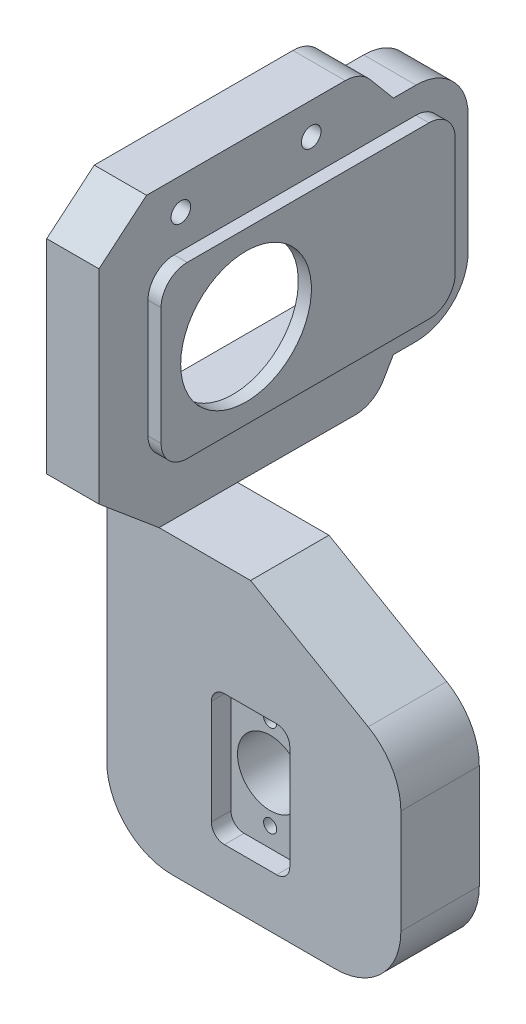
SolidWorks part; units mm, degrees
note: The reader was unsure of these and kept them because the rebuilt part matched: shared geometry of "Sketch1<3>", "Sketch1<4>", "Sketch3<4>", "Sketch3<6>", "Sketch3<7>".
other "Markup1"
sketch "Sketch8" plane through (0, 0, -51.7836) normal (-1, 0, 0) x (0, 0, 1)
material "ABS"
ref_plane "Front Plane" through (0, 0, 0) normal (0, 0, 1) x (1, 0, 0)
ref_plane "Top Plane" through (0, 0, 0) normal (0, 1, 0) x (1, 0, 0)
ref_plane "Right Plane" through (0, 0, 0) normal (1, 0, 0) x (0, 0, -1)
sketch "Sketch1" plane through (0, 0, 0) normal (0, 0, 1) x (1, 0, 0)
  line L0 (0, 45) -> (0, 10)
  line L1 (10, 0) -> (35, 0)
  line L2 (45, 10) -> (45, 25.9474)
  line L3 (40, 34.6077) -> (22, 45)
  line L4 (22, 45) -> (0, 45)
  line L6 (18, 8) -> (26, 8)
  line L7 (16, 10) -> (16, 26)
  line L8 (18, 28) -> (26, 28)
  line L9 (28, 10) -> (28, 26)
  line L10 (16, 8) -> (28, 28) construction
  line L11 (16, 28) -> (28, 8) construction
  circle A0 centre (22, 18) radius 5
  circle A1 centre (22, 11) radius 1
  circle A2 centre (22, 25) radius 1
  arc A3 (18, 8) -> (16, 10) centre (18, 10) cw
  arc A4 (26, 8) -> (28, 10) centre (26, 10) ccw
  arc A5 (26, 28) -> (28, 26) centre (26, 26) cw
  arc A6 (16, 26) -> (18, 28) centre (18, 26) cw
  arc A11 (45, 25.9474) -> (40, 34.6077) centre (35, 25.9474) ccw
  arc A12 (0, 10) -> (10, 0) centre (10, 10) ccw
  arc A13 (35, 0) -> (45, 10) centre (35, 10) ccw
  point P44 (0, 0)
  point P47 (45, 0)
  dimension "D5" = 10
  dimension "D7" = 2
  dimension "D4" = 2
  dimension "D16" = 10
  dimension "D1" = 45
  dimension "D2" = 45
  dimension "D3" = 120
  dimension "D6" = 7
  dimension "D8" = 7
  dimension "D9" = 27
  dimension "D10" = 22
  dimension "D11" = 20
  dimension "D12" = 11
  dimension "D13" = 6
  dimension "D14" = 10
extrude "Boss-Extrude1" add sketch "Sketch1" against normal blind 12 contours L4 L0 A12 L1 A13 L2 A11 L3
extrude "Cut-Extrude1" cut sketch "Sketch1<3>" against normal blind 3 contours A2 | A6 L7 A3 L6 A4 L9 A5 L8 A2 A1 | A1 | A0
sketch "Sketch1<3>" plane through (0, 0, 0) normal (0, 0, 1) x (1, 0, 0) same geometry as "Sketch1"
extrude "Cut-Extrude2" cut sketch "Sketch1<4>" against normal through all contours A2 | A1 | A0
sketch "Sketch1<4>" plane through (0, 0, 0) normal (0, 0, 1) x (1, 0, 0) same geometry as "Sketch1"
sketch "Sketch3" plane through (0, 0, 0) normal (-1, 0, 0) x (0, 0, 1)
  line L0 (9.1925, 52.7135) -> (0, 45)
  line L1 (9.1925, 83.8935) -> (9.1925, 52.7135)
  line L2 (9.1925, 83.8935) -> (1.9151, 90)
  line L3 (1.9151, 90) -> (-28.4826, 90)
  line L4 (-32.3129, 88.2139) -> (-35.8509, 83.9975)
  line L6 (-41.3075, 76) -> (-41.3075, 58)
  line L8 (-34.3402, 47.4081) -> (-35.8509, 50)
  line L9 (-29.9998, 44.926) -> (-12, 45)
  line L10 (-0.3075, 76) -> (-0.3075, 58)
  line L15 (-47.3075, 75.9975) -> (-47.3075, 58)
  line L16 (-39.3075, 50) -> (-2.3075, 50)
  line L19 (5.6925, 75.9975) -> (5.6925, 58)
  line L21 (-12, 45) -> (0, 45)
  line L26 (-39.3075, 56) -> (-2.3075, 56)
  line L33 (-43.3075, 75.9975) -> (-43.3075, 58)
  line L34 (-39.3075, 54) -> (-2.3075, 54)
  line L35 (1.6925, 75.9975) -> (1.6925, 58)
  line L39 (-39.3075, 78) -> (-2.3075, 78)
  line L53 (-39.3075, 83.9975) -> (-2.3075, 83.9975)
  line L55 (-39.3075, 79.9975) -> (-2.3075, 79.9975)
  circle A0 centre (-11.3075, 67) radius 10
  arc A3 (-41.3075, 76) -> (-39.3075, 78) centre (-39.3075, 76) cw
  arc A5 (-34.3402, 47.4081) -> (-29.9998, 44.926) centre (-30.0204, 49.9259) ccw
  arc A12 (-43.3075, 75.9975) -> (-39.3075, 79.9975) centre (-39.3075, 75.9975) cw
  arc A14 (-0.3075, 58) -> (-2.3075, 56) centre (-2.3075, 58) cw
  arc A16 (-39.3075, 56) -> (-41.3075, 58) centre (-39.3075, 58) cw
  arc A21 (-43.3075, 58) -> (-39.3075, 54) centre (-39.3075, 58) ccw
  arc A22 (1.6925, 58) -> (-2.3075, 54) centre (-2.3075, 58) cw
  arc A23 (-2.3075, 79.9975) -> (1.6925, 75.9975) centre (-2.3075, 75.9975) cw
  arc A24 (-47.3075, 75.9975) -> (-39.3075, 83.9975) centre (-39.3075, 75.9975) cw
  circle A25 centre (-34.8075, 67) radius 5 construction
  arc A28 (-47.3075, 58) -> (-39.3075, 50) centre (-39.3075, 58) ccw
  arc A29 (-2.3075, 78) -> (-0.3075, 76) centre (-2.3075, 76) cw
  arc A32 (-28.4826, 90) -> (-32.3129, 88.2139) centre (-28.4826, 85) ccw
  arc A33 (5.6925, 58) -> (-2.3075, 50) centre (-2.3075, 58) cw
  arc A36 (-2.3075, 83.9975) -> (5.6925, 75.9975) centre (-2.3075, 75.9975) cw
  point P26 (-2.1748, 77.825)
  point P53 (-0.3075, 56.5128)
  dimension "D4" = 11
  dimension "D13" = 130
  dimension "D15" = 53
  dimension "D18" = 10
  dimension "D8" = 25.9975
  dimension "D22" = 2
  dimension "D16" = 45
  dimension "D25" = 2
  dimension "D26" = 4
  dimension "D27" = 8
  dimension "D7" = 22
  dimension "D31" = 8
  dimension "D20" = 8
  dimension "D34" = 4
  dimension "D32" = 4
  dimension "D39" = 4
  dimension "D42" = 4
  dimension "D6" = 20
  dimension "D21" = 4
  dimension "D30" = 5
  dimension "D36" = 2
  dimension "D43" = 8
  dimension "D52" = 5
  dimension "D1" = 53
  dimension "D5" = 23.5
  dimension "D9" = 33.9975
  dimension "D10" = 45
  dimension "D11" = 45
  dimension "D12" = 9.5
  dimension "D14" = 12
  dimension "D17" = 41
  dimension "D19" = 6.5
  dimension "D24" = 4
  dimension "D28" = 12.5
  dimension "D29" = 5.5042
  dimension "D33" = 45
  dimension "D35" = 130
  dimension "D40" = 13
  dimension "D23" = 2
  dimension "D44" = 18
  dimension "D45" = 6
  dimension "D46" = 120
  dimension "D47" = 130
  dimension "D48" = 4
  dimension "D49" = 2
  dimension "D50" = 11
  dimension "D51" = 3
  dimension "D53" = 140
  dimension "D54" = 130
  dimension "D55" = 20.5
  dimension "D56" = 12.5
  dimension "D57" = 11
extrude "Boss-Extrude2" add sketch "Sketch3" against normal blind 8
extrude "Boss-Extrude3" add sketch "Sketch3<4>" against normal blind 10
sketch "Sketch3<4>" plane through (0, 0, 0) normal (-1, 0, 0) x (0, 0, 1) same geometry as "Sketch3"
extrude "Cut-Extrude5" cut sketch "Sketch3<6>" against normal blind 8
sketch "Sketch3<6>" plane through (0, 0, 0) normal (-1, 0, 0) x (0, 0, 1) same geometry as "Sketch3"
extrude "Cut-Extrude6" cut sketch "Sketch3<7>" against normal through all contours A0
sketch "Sketch3<7>" plane through (0, 0, 0) normal (-1, 0, 0) x (0, 0, 1) same geometry as "Sketch3"
sketch "Sketch7" plane through (0, 0, 0) normal (-1, 0, 0) x (0, 0, 1)
  line L0 (-41.3075, 76) -> (-41.3075, 58) construction
  line L1 (-0.3075, 76) -> (-0.3075, 58) construction
  line L2 (-39.3075, 56) -> (-2.3075, 56) construction
  circle A0 centre (-44.3075, 72) radius 1.2804
  circle A1 centre (-44.3075, 62) radius 1.2804
  circle A2 centre (2.6925, 62) radius 1.2804
  circle A3 centre (2.6925, 72) radius 1.2804
  dimension "D1" = 2.5608
  dimension "D2" = 3
  dimension "D3" = 3
  dimension "D4" = 3
  dimension "D5" = 10
  dimension "D6" = 6
extrude "Cut-Extrude7" cut sketch "Sketch7" against normal blind 3 contours A0
sketch "Sketch11" plane through (8, 0, 0) normal (1, 0, 0) x (0, 0, -1)
  line L0 (39.3075, 79.9975) -> (2.3075, 79.9975) construction
  line L1 (-9.1925, 83.8935) -> (-9.1925, 52.7135) construction
  circle A0 centre (0.8075, 84.4975) radius 3
  circle A1 centre (24.8075, 84.4975) radius 3
  dimension "D1" = 6
  dimension "D5" = 6
  dimension "D2" = 4.5
  dimension "D3" = 24
  dimension "D4" = 10
extrude "Boss-Extrude4" [suppressed] add sketch "Sketch11" along normal blind 3
sketch "Sketch9" plane through (8, 0, 0) normal (1, 0, 0) x (0, 0, -1)
  line L0 (13.2838, 90) -> (13.2838, 44.9947) construction
  line L2 (39.3075, 79.9975) -> (2.3075, 79.9975) construction
  line L3 (-1.9151, 90) -> (28.4826, 90) construction
  line L4 (29.9998, 44.926) -> (12, 45) construction
  line L5 (47.3075, 66.9987) -> (-9.1925, 66.9987) construction
  line L6 (47.3075, 75.9975) -> (47.3075, 58) construction
  line L7 (-9.1925, 83.8935) -> (-9.1925, 52.7135) construction
  line L8 (19.0575, 90) -> (19.0575, 44.971) construction
  circle A0 centre (3.3338, 85.1475) radius 1.5
  circle A1 centre (23.2838, 85.1475) radius 1.5
  dimension "D1" = 3
  dimension "D2" = 5.15
  dimension "D3" = 9.95
  dimension "D4" = 10
extrude "Cut-Extrude8" cut sketch "Sketch9" against normal through all both and the other way through all
